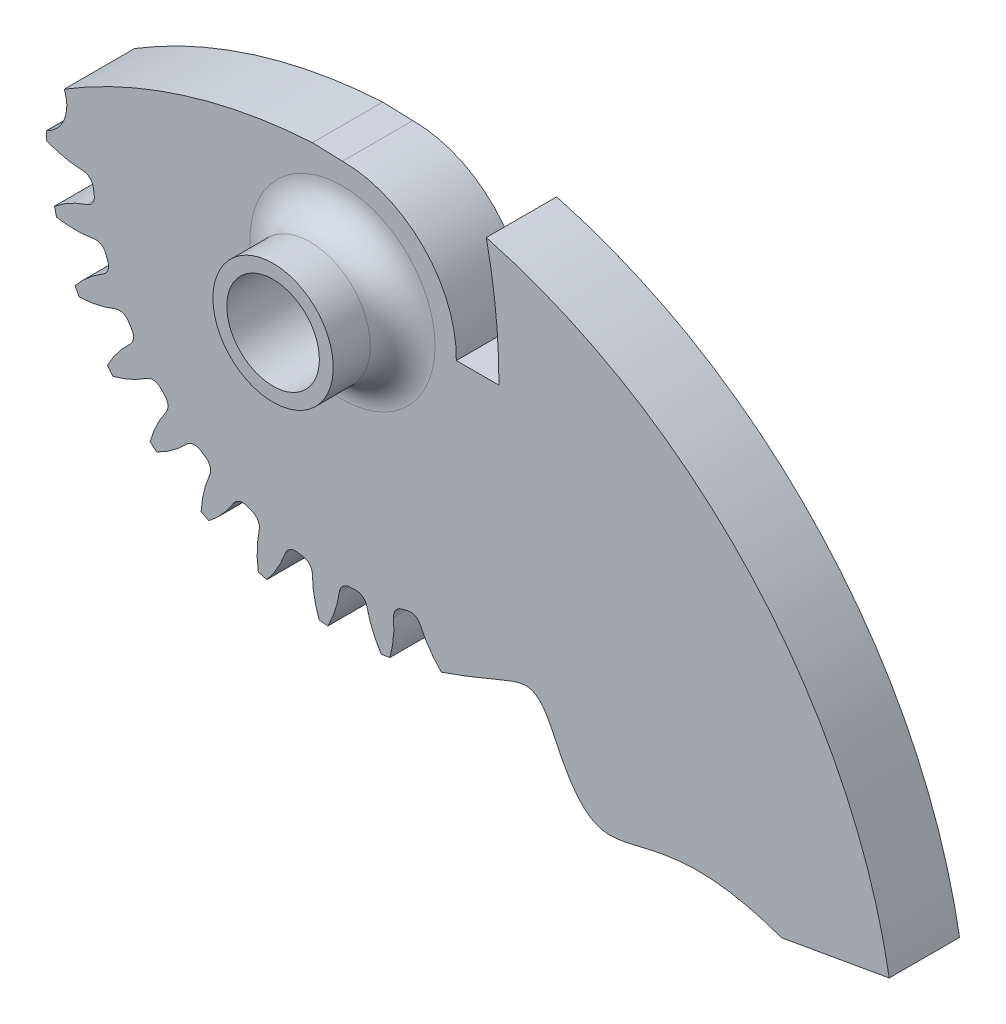
SolidWorks part; units mm, degrees
material "ABS"
ref_plane "Front" through (0, 0, 0) normal (0, 0, 1) x (1, 0, 0)
ref_plane "Top" through (0, 0, 0) normal (0, 1, 0) x (1, 0, 0)
ref_plane "Right" through (0, 0, 0) normal (1, 0, 0) x (0, 0, -1)
sketch "Sketch3" plane through (0, 0, 0) normal (0, 0, 1) x (1, 0, 0)
  circle A0 centre (0, 0) radius 40.64
  dimension "od" = 40.64
extrude "gearBody" add sketch "Sketch3" along normal blind 9.652
sketch "Sketch2" plane through (0, 0, 0) normal (0, 0, 1) x (1, 0, 0)
  line L0 (0, 0) -> (34.0786, 14.1158) construction
  line L1 (45.4751, -11.4855) -> (0, 0) construction
  line L2 (0, 0) -> (36.3143, 0) construction
  line L3 (38.0972, -0.458) -> (37.8451, -4.4001) construction
  line L5 (37.9712, -2.4291) -> (0, 0) construction
  line L7 (0, 0) -> (36.8864, 0) construction
  arc A0 (36.879, -0.7403) -> (36.6727, -3.9649) centre (0, 0) ccw construction
  arc A1 (40.637, 0.4947) -> (40.2427, -5.6687) centre (0, 0) ccw construction
  arc A2 (38.0972, -0.458) -> (37.8451, -4.4001) centre (0, 0) ccw construction
  arc A3 (34.9015, -2.6404) -> (34.9534, -1.8283) centre (0, 0) ccw construction
  arc A4 (45.4751, -11.4855) -> (35.6466, -3.6712) centre (32.0022, -18.3431) ccw construction
  arc A5 (45.4751, -11.4855) -> (46.5679, 5.5974) centre (0, 0) ccw construction
  arc A6 (46.5679, 5.5974) -> (35.8238, -0.9008) centre (34.0786, 14.1158) cw construction
  arc A7 (34.9534, -1.8283) -> (35.8238, -0.9008) centre (35.9376, -1.8798) cw construction
  arc A8 (35.6466, -3.6712) -> (34.9015, -2.6404) centre (35.8842, -2.7147) cw construction
  arc A9 (46.8801, 7.0756) -> (35.7652, -0.3962) centre (34.0786, 14.1158) cw
  arc A10 (34.4461, -1.8018) -> (35.7652, -0.3962) centre (35.9376, -1.8798) cw
  arc A11 (34.3949, -2.6021) -> (34.4461, -1.8018) centre (0, 0) ccw
  arc A12 (35.5241, -4.1642) -> (34.3949, -2.6021) centre (35.8842, -2.7147) cw
  arc A13 (45.5964, -12.9914) -> (35.5241, -4.1642) centre (32.0022, -18.3431) ccw
  arc A14 (45.5964, -12.9914) -> (46.8801, 7.0756) centre (0, 0) ccw
  point P6 (46.5679, 5.5974)
  point P22 (45.4751, -11.4855)
  dimension "D1" = 0.508
  dimension "baseDia" = 73.7729
  dimension "od" = 81.28
  dimension "pd" = 76.2
  dimension "rd" = 70.0024
  dimension "rFillet" = 0.9855
  dimension "pointX" = 46.5679
  dimension "pointY" = 5.5974
  dimension "CTT" = 3.9421
  dimension "flankCenterAngle" = 22.5
extrude "toothCut" cut sketch "Sketch2" along normal through all
pattern_circular "CirPattern1" count 30 over 360 about axis through (0, 0, 9.652) along (0, 0, -1) of "toothCut"
sketch "hub1Dia" plane through (0, 0, 0) normal (0, 0, -1) x (-1, 0, 0)
  circle A0 centre (0, 0) radius 12.7
  dimension "hub1Dia" = 25.4
sketch "hub2Dia" plane through (0, 0, 9.652) normal (0, 0, 1) x (1, 0, 0)
  circle A0 centre (0, 0) radius 12.7
  dimension "hub2dia" = 25.4
sketch "boreDia" plane through (0, 0, 0) normal (0, 0, 1) x (1, 0, 0)
  circle A0 centre (0, 0) radius 6.7469
  dimension "boreDia" = 13.4937
extrude "bore" cut sketch "boreDia" against normal mid plane 25400
sketch "Sketch4" plane through (0, 0, 9.652) normal (0, 0, 1) x (1, 0, 0)
  circle A0 centre (0, -57.15) radius 76.1746
  arc A2 (-41.7195, 6.5842) -> (41.7195, 6.5842) centre (0, 0) cw
  dimension "D1" = 152.3492
  dimension "D2" = 57.15
extrude "Cut-Extrude1" cut sketch "Sketch4" against normal through all contours A0 region at (0, 26.0638, 9.652)
sketch "Sketch5" plane through (0, 0, 9.652) normal (0, 0, 1) x (1, 0, 0)
  line L0 (0, 19.0246) -> (21.5163, 3.7176)
  line L1 (21.5163, 3.7176) -> (10.4433, -33.7781)
  line L2 (10.4433, -33.7781) -> (13.558, -38.3117)
  line L3 (0, 0) -> (0, -57.15) construction
  line L4 (0, -57.15) -> (-54.1615, -3.586) construction
  line L5 (0, -57.15) -> (65.9691, -95.2373) construction
  line L9 (0, -57.15) -> (75.0173, -43.9224) construction
  line L12 (60.232, -46.5295) -> (75.0173, -43.9224)
  line L13 (0, -57.15) -> (29.696, -40.005) construction
  line L14 (29.696, -40.005) -> (26.521, -34.5057) construction
  circle A1 centre (0, -57.15) radius 76.1746 construction
  arc A5 (0, 19.0246) -> (75.0173, -43.9224) centre (0, -57.15) cw
  circle A6 centre (0, -57.15) radius 21.59 construction
  arc A9 (10.6752, -34.1372) -> (8.9309, -33.317) centre (9.3176, -34.7596) ccw construction
  circle A12 centre (49.4934, -85.725) radius 40.64 construction
  spline S0 degree 3 poles (13.558, -38.3117) (21.087, -35.7646) (26.3659, -31.8249) (36.3578, -56.1686) (39.5345, -39.0169) (60.232, -46.5295) knots 0 0 0 0 0.118515 0.218515 1 1 1 1
  point P10 (13.028, -38.4952)
  point P16 (13.558, -38.3117)
  point P18 (7.4375, -28.992)
  point P19 (10.4433, -33.7781)
  point P28 (21.569, -56.1981)
  dimension "D1" = 43.18
  dimension "D3" = 81.28
  dimension "D6" = 152.3492
  dimension "D2" = 120
  dimension "D4" = 57.15
  dimension "D8" = 57.15
  dimension "D7" = 60
  dimension "D9" = 34.29
  dimension "D10" = 6.35
  dimension "D5" = 80
extrude "Boss-Extrude1" add sketch "Sketch5" against normal up to surface (9.652 mm away) up to face at (6.7469, 0, 0)
sketch "Sketch6" plane through (0, 0, 9.652) normal (0, 0, 1) x (1, 0, 0)
  line L1 (-41.2993, 3.0747) -> (-42.3397, 6.1739)
  line L2 (15.875, 0) -> (21.209, 0)
  circle A0 centre (0, -57.15) radius 76.1746 construction
  arc A1 (75.0173, -43.9224) -> (-33.55, 11.2383) centre (0, -57.15) ccw construction
  circle A2 centre (0, 0) radius 15.875 construction
  arc A3 (0, 15.875) -> (15.875, 0) centre (0, 0) cw
  arc A4 (19.4523, 16.499) -> (-42.3397, 6.1739) centre (0, -57.15) ccw
  arc A5 (0, 15.875) -> (-41.2993, 3.0747) centre (0, -57.15) ccw
  circle A6 centre (0, 0) radius 21.209 construction
  circle A8 centre (-57.15, 0) radius 78.359 construction
  arc A9 (21.209, 0) -> (19.4523, 16.499) centre (-57.15, 0) ccw
  dimension "D4" = 57.15
  dimension "D1" = 31.75
  dimension "D2" = 42.418
  dimension "D3" = 156.718
extrude "Cut-Extrude2" cut sketch "Sketch6" against normal through all
sketch "Sketch7" plane through (0, 0, 9.652) normal (0, 0, 1) x (1, 0, 0)
  circle A0 centre (0, 0) radius 6.7469
  circle A1 centre (0, 0) radius 6.7469 construction
  circle A2 centre (0, 0) radius 8.255
  dimension "D1" = 16.51
extrude "spacer" add sketch "Sketch7" along normal blind 9.525
fillet "Fillet1" radius 4.445 1 edges at (8.255, 0, 9.652)
sketch "Sketch8" plane through (0, 0, 9.652) normal (0, 0, 1) x (1, 0, 0)
  line L0 (-38.1756, 5.1017) -> (-34.0224, 5.3247)
  line L1 (-34.0224, 5.3247) -> (-34.2899, 0.0545)
  line L2 (-34.2899, 0.0545) -> (-40.6263, -1.0555)
  arc A0 (-38.1756, 5.1017) -> (-40.6263, -1.0555) centre (-42.6187, 3.3039) cw
  point P3 (-38.6884, 4.7843)
  point P8 (-38.1756, 5.1017)
  point P10 (-40.637, -0.4947)
  point P11 (-40.6263, -1.0555)
extrude "overextension stop" add sketch "Sketch8" against normal up to surface (9.652 mm away) up to face at (-13.508, -22.4485, 0)
sketch "Sketch9" plane through (0, 0, 9.652) normal (0, 0, 1) x (1, 0, 0)
  line L0 (15.875, 0) -> (21.209, 0) construction
  line L1 (15.6189, -0.254) -> (21.4626, -0.254)
  line L2 (0, 15.621) -> (-4.136, 15.7578)
  line L4 (19.4523, 16.499) -> (19.7006, 16.5525) construction
  line L5 (-4.136, 15.7578) -> (12.1122, 22.771)
  line L6 (12.1122, 22.771) -> (19.7006, 16.5525)
  arc A0 (19.4523, 16.499) -> (21.209, 0) centre (-57.15, 0) cw construction
  arc A1 (15.875, 0) -> (0, 15.875) centre (0, 0) ccw construction
  arc A2 (19.7006, 16.5525) -> (21.4626, -0.254) centre (-57.15, 0) cw
  arc A3 (15.6189, -0.254) -> (0, 15.621) centre (0, 0) ccw
  arc A4 (0, 15.875) -> (-38.1756, 5.1017) centre (0, -57.15) ccw construction
extrude "body tube cutout clearance" cut sketch "Sketch9" against normal through all both
sketch "Sketch10" plane through (0, 0, 9.652) normal (0, 0, 1) x (1, 0, 0)
  circle A0 centre (0, 0) radius 6.35
  circle A1 centre (0, 0) radius 7.3025
  dimension "D1" = 12.7
  dimension "D2" = 14.605
extrude "bore dia" add sketch "Sketch10" along normal up to surface and the other way up to surface up to face at (8.255, 0, 19.177) other way up to face at (-12.4855, -23.0996, 0)
equation "\"Bodytube_OD\"= 6.17in"
equation "\"Bodytube_ID\"= 5.998in"
equation "\"Fwd_Tube_Length\"= 40in"
equation "\"Mid_Tube_Length\"= 1in"
equation "\"Aft_Section_Length\"= 39in"
equation "\"Mid_Coupler_Length\"= 13in"
equation "\"Aft_Lower_Length\"= 22in"
equation "\"AB_Coupler_OD_Length\"= 1in"
equation "\"AB_Coupling_Section_Length\"= 0.375in"
equation "\"AB_Coupler_Length\"= \"AB_Coupler_OD_Length\" + \"AB_Coupling_Section_Length\" * 2"
equation "\"Cutout_Angle\"= 80"
equation "\"AB_Paddle_Height\"= 0.375in"
equation "\"AB_Coupler_Num_Screws\"= 4"
equation "\"Num_Cutouts\"= 3"
equation "\"AB_Coupler_OD\"= 6.17in"
equation "\"AB_Coupler_ID\"= 5.75in"
equation "\"AB_Coupler_Surface_Diameter\"= 5.998in"
equation "\"AB_Coupling_Screw_Diameter\"= 0.15748in"
equation "\"AB_Central_Bushing_Length\"= .4724in"
equation "\"Lead_Screw_Dist\"= 3.4in"
equation "\"Lead_Screw_Diam\"= 0.386in"
equation "\"Lead_Screw_Length\"= (\"Mid_Coupler_Length\" + 2*0.375in + 2*0.5in)"
equation "\"Paddle_Pin_Offset\"= .25in"
equation "\"Paddle_Pin_Radius\"= 2.25in"
equation "\"Fwd_BKHD_From_Top\"= 18in"
equation "\"D1@Sketch4\"=\"Bodytube_ID\""
equation "\"D2@Sketch4\"=\"Paddle_Pin_Radius\""
equation "\"D3@Sketch5\"=\"Paddle_Gear_OD\""
equation "\"D4@Sketch5\"=\"Paddle_Pin_Radius\""
equation "\"Motor_OD\"= 4in"
equation "\"Aft_Upper_Length\"= \"Aft_Section_Length\" - \"Aft_Lower_Length\" - \"AB_Coupler_OD_Length\""
equation "\"Paddle_Gear_OD\"= 3.2in"
equation "\"D5@Sketch5\"=\"Cutout_Angle\""
equation "\"D6@Sketch5\"=\"Bodytube_ID\""
equation "\"D1@Sketch6\"=\"AB_Coupler_ID\"-2*\"Paddle_Pin_Radius\""
equation "\"D2@Sketch6\"=\"Bodytube_OD\"-2*\"Paddle_Pin_Radius\""
equation "\"D3@Sketch6\"=\"Bodytube_OD\""
equation "\"D4@Sketch6\"=\"Paddle_Pin_Radius\""
equation "\"D8@Sketch5\"=\"Paddle_Pin_Radius\""
equation "\"Drive_Gear_OD\"= 1.7in"
equation "\"Fin_Thickness\"= .118in"
equation "\"Guiderail_Cutout_Diameter\"= 1.5in"
equation "\"DB9_Hole_Dist\"= 25mm"
equation "\"D1@Sketch5\"=\"Drive_Gear_OD\""
